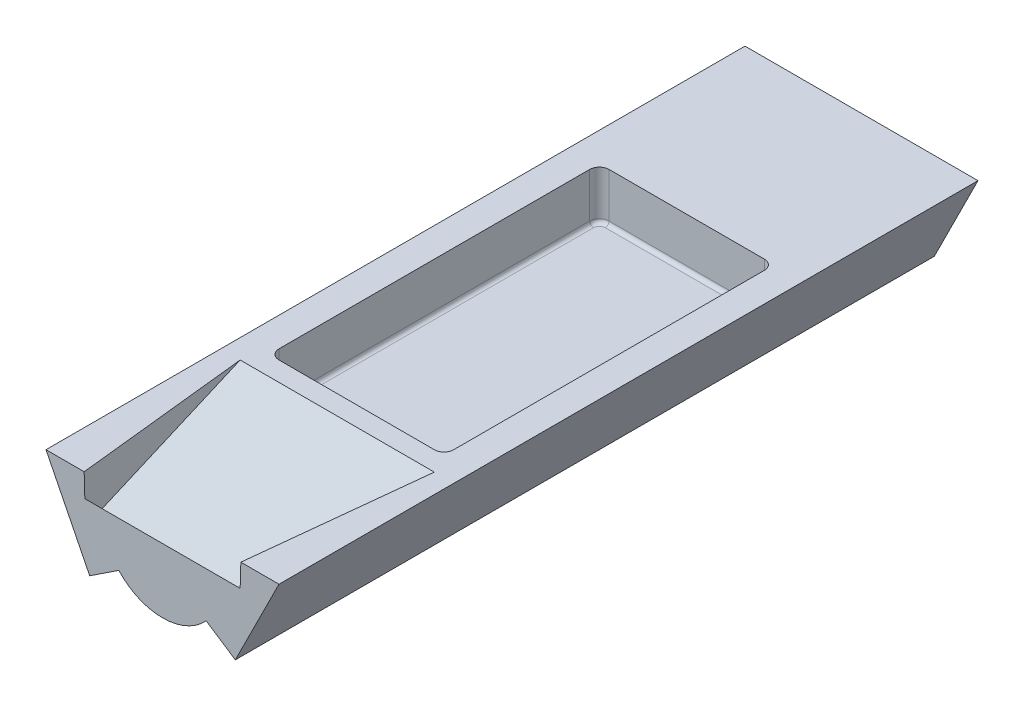
SolidWorks part; units mm, degrees
ref_plane "Front Plane" through (0, 0, 0) normal (0, 0, 1) x (1, 0, 0)
ref_plane "Top Plane" through (0, 0, 0) normal (0, 1, 0) x (1, 0, 0)
ref_plane "Right Plane" through (0, 0, 0) normal (1, 0, 0) x (0, 0, -1)
sketch "Sketch1" plane through (0, 0, 0) normal (0, 0, 1) x (1, 0, 0)
  line L6 (-304.8, 228.6) -> (304.8, 228.6)
  line L9 (0, 0) -> (0, 228.6) construction
  line L15 (-304.8, 228.6) -> (-190.5, 0)
  line L16 (-190.5, 0) -> (-114.3, 50.4)
  line L18 (190.5, 0) -> (304.8, 228.6)
  line L19 (190.5, 0) -> (114.3, 50.4)
  arc A0 (-114.3, 50.4) -> (114.3, 50.4) centre (0, 154.808) ccw
  dimension "D1" = 609.6
  dimension "D2" = 228.6
  dimension "D3" = 228.6
  dimension "D4" = 114.3
  dimension "D5" = 114.3
  dimension "D6" = 76.2
  dimension "D7" = 76.2
extrude "Boss-Extrude2" add sketch "Sketch1" against normal blind 1828.8
sketch "Sketch2" plane through (0, 228.6, 0) normal (0, 1, 0) x (1, 0, 0)
  line L1 (-203.2, 0) -> (203.2, 0)
  line L3 (-254, 457.2) -> (254, 457.2)
  line L6 (-254, 457.2) -> (-203.2, 0)
  line L7 (254, 457.2) -> (203.2, 0)
  line L8 (304.8, 0) -> (-304.8, 0) construction
  dimension "D1" = 508
  dimension "D2" = 457.2
  dimension "D3" = 50.8
  dimension "D4" = 50.8
ref_plane "Plane1" through (0, 98.9867, 26.5234) normal (0, 0.9659, 0.2588) x (1, 0, 0)
sketch "Sketch7" plane through (0, 98.9867, 26.5234) normal (0, 0.9659, 0.2588) x (1, 0, 0)
  line L0 (-203.2, 43.5873) -> (203.2, 43.5873)
  line L1 (-254, 500.7873) -> (254, 500.7873)
  line L2 (-254, 500.7873) -> (-203.2, 43.5873)
  line L3 (254, 500.7873) -> (203.2, 43.5873)
  point P4 (254, 500.7873)
  dimension "D1" = 508
  dimension "D2" = 457.2
  dimension "D3" = 50.8
  dimension "D4" = 50.8
extrude "Cut-Extrude2" cut sketch "Sketch7" along normal through all
sketch "Sketch8" plane through (0, 228.6, 0) normal (0, 1, 0) x (1, 0, 0)
  line L0 (-304.8, 1828.8) -> (-304.8, 0) construction
  line L1 (-228.6, 508) -> (228.6, 508)
  line L2 (-228.6, 508) -> (-228.6, 1371.6)
  line L3 (-228.6, 1371.6) -> (228.6, 1371.6)
  line L4 (228.6, 508) -> (228.6, 1371.6)
  line L5 (254, 457.2) -> (-254, 457.2) construction
  dimension "D1" = 457.2
  dimension "D2" = 863.6
  dimension "D3" = 76.2
  dimension "D4" = 50.8
extrude "Cut-Extrude5" cut sketch "Sketch8" against normal blind 127
fillet "Fillet1" radius 10 4 edges at (0, 101.6, -1371.6) (228.6, 101.6, -939.8) (0, 101.6, -508) (-228.6, 101.6, -939.8)
fillet "Fillet2" radius 25.4 8 edges at (225.6711, 104.5289, -510.9289) (-225.6711, 104.5289, -510.9289) (-228.6, 170.1, -508) (228.6, 170.1, -508) (-225.6711, 104.5289, -1368.6711) (225.6711, 104.5289, -1368.6711) (228.6, 170.1, -1371.6) (-228.6, 170.1, -1371.6)
